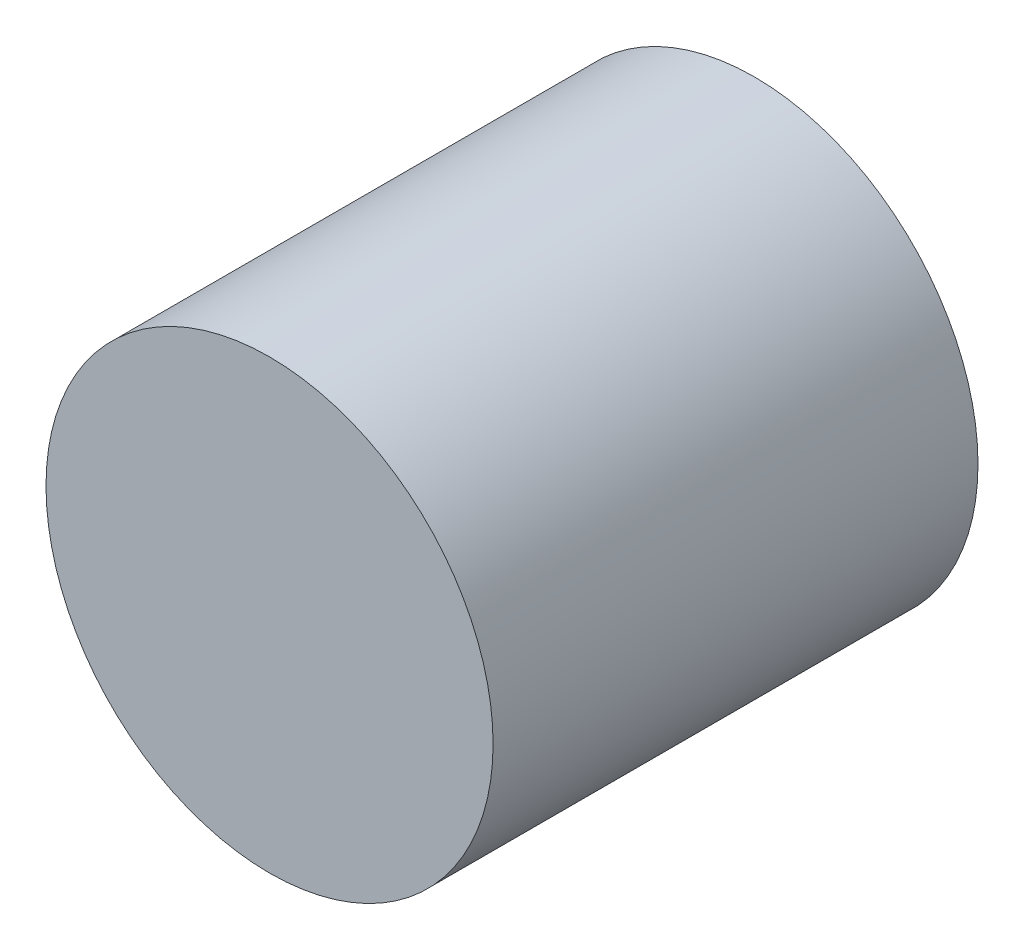
SolidWorks part; units mm, degrees
ref_plane "Front Plane" through (0, 0, 0) normal (0, 0, 1) x (1, 0, 0)
ref_plane "Top Plane" through (0, 0, 0) normal (0, 1, 0) x (1, 0, 0)
ref_plane "Right Plane" through (0, 0, 0) normal (1, 0, 0) x (0, 0, -1)
sketch "Sketch1" plane through (0, 0, 0) normal (0, 0, 1) x (1, 0, 0)
  circle A0 centre (0, 0) radius 49.53
  dimension "D1" = 99.06
extrude "Boss-Extrude1" add sketch "Sketch1" along normal blind 107.442
